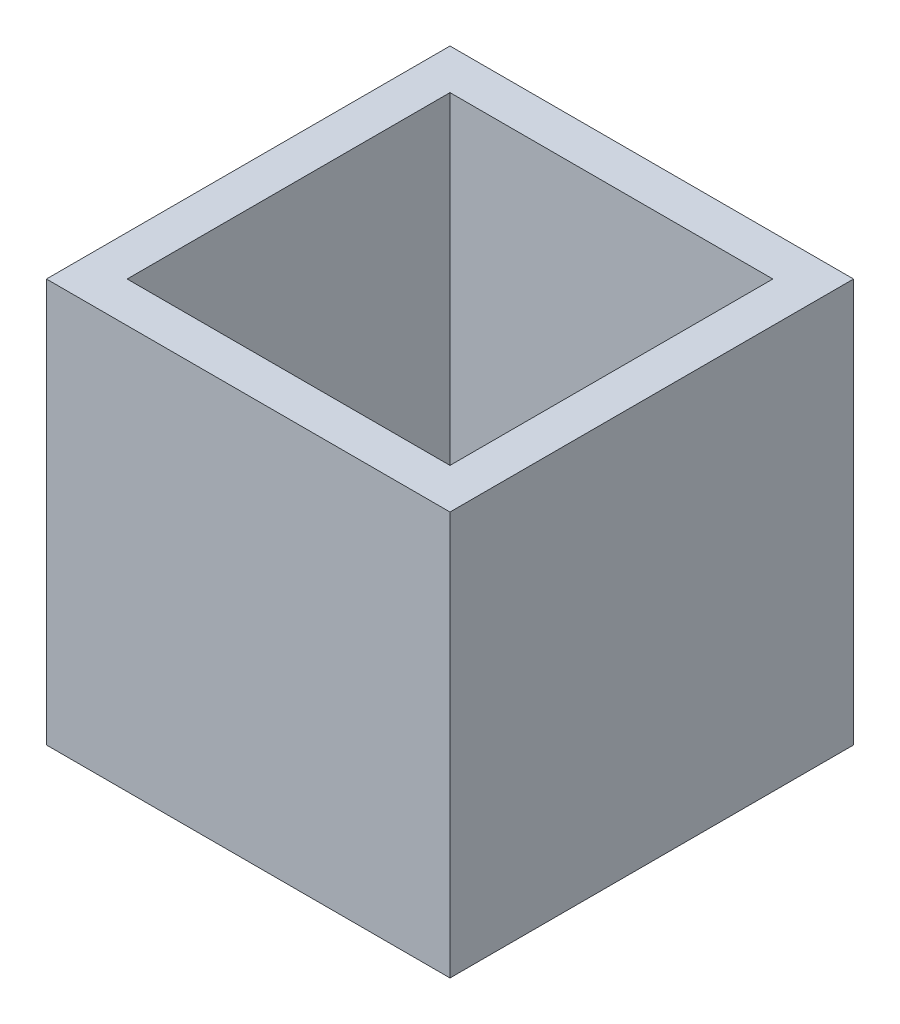
SolidWorks part; units mm, degrees
ref_plane "Front Plane" through (0, 0, 0) normal (0, 0, 1) x (1, 0, 0)
ref_plane "Top Plane" through (0, 0, 0) normal (0, 1, 0) x (1, 0, 0)
ref_plane "Right Plane" through (0, 0, 0) normal (1, 0, 0) x (0, 0, -1)
sketch "Sketch1" plane through (0, 0, 0) normal (0, 1, 0) x (1, 0, 0)
  line L1 (-1.25, -1.25) -> (1.25, -1.25)
  line L2 (-1.25, -1.25) -> (-1.25, 1.25)
  line L3 (-1.25, 1.25) -> (1.25, 1.25)
  line L4 (1.25, -1.25) -> (1.25, 1.25)
  line L5 (-1.25, -1.25) -> (1.25, 1.25) construction
  line L6 (-1.25, 1.25) -> (1.25, -1.25) construction
  line L7 (-1, -1) -> (1, -1)
  line L8 (-1, -1) -> (-1, 1)
  line L9 (-1, 1) -> (1, 1)
  line L10 (1, -1) -> (1, 1)
  line L11 (-1, -1) -> (1, 1) construction
  line L12 (-1, 1) -> (1, -1) construction
  point P0 (0, 0)
  point P6 (0, 0)
  dimension "D1" = 2.5
  dimension "D2" = 2.5
  dimension "D3" = 2
extrude "Boss-Extrude1" add sketch "Sketch1" along normal blind 2.5
